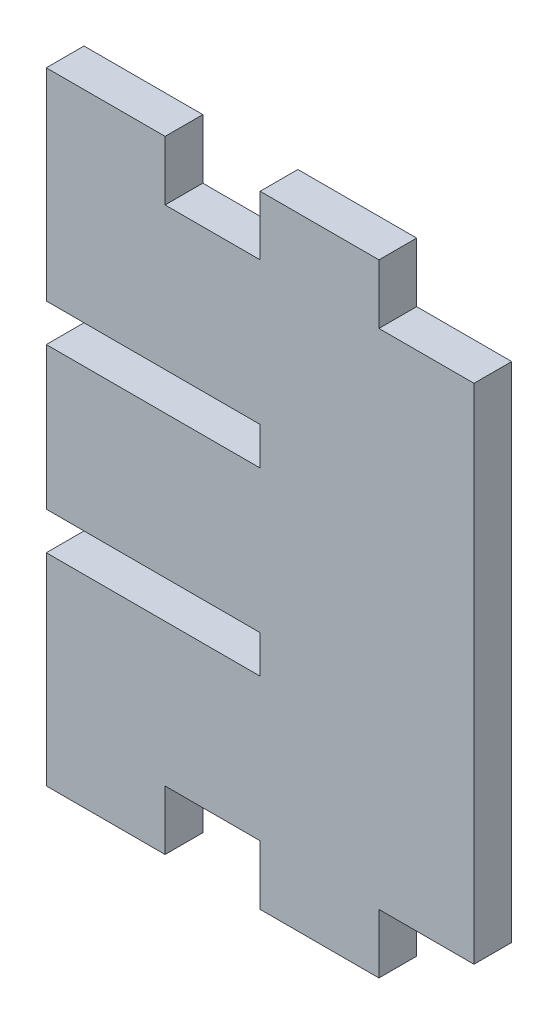
SolidWorks part; units mm, degrees
ref_plane "Front Plane" through (0, 0, 0) normal (0, 0, 1) x (1, 0, 0)
ref_plane "Top Plane" through (0, 0, 0) normal (0, 1, 0) x (1, 0, 0)
ref_plane "Right Plane" through (0, 0, 0) normal (1, 0, 0) x (0, 0, -1)
sketch "Sketch1" plane through (0, 0, 0) normal (0, 0, 1) x (1, 0, 0)
  line L0 (0, 0) -> (60.2571, 0) construction
  line L1 (55, 0) -> (-55, 0) construction
  line L2 (-18, -6) -> (-18, 6)
  line L3 (-18, 6) -> (0, 6)
  line L4 (0, 6) -> (0, 9.175)
  line L5 (0, 9.175) -> (-18, 9.175)
  line L6 (-18, 9.175) -> (-18, 26.175)
  line L7 (0, -55) -> (0, 55) construction
  line L8 (0, 1.5761) -> (0, 45.6913) construction
  line L9 (-18, 26.175) -> (-8, 26.175)
  line L10 (0, 26.175) -> (0, 21.175)
  line L11 (0, 21.175) -> (-8, 21.175)
  line L12 (-8, 21.175) -> (-8, 26.175)
  line L13 (0, 26.175) -> (10, 26.175)
  line L14 (10, 26.175) -> (10, 21.175)
  line L15 (10, 21.175) -> (18, 21.175)
  line L16 (18, 21.175) -> (18, -21.175)
  line L17 (-18, -6) -> (0, -6)
  line L18 (0, -6) -> (0, -9.175)
  line L19 (0, -9.175) -> (-18, -9.175)
  line L20 (-18, -9.175) -> (-18, -26.175)
  line L21 (0, -26.175) -> (0, -21.175)
  line L22 (-18, -26.175) -> (-8, -26.175)
  line L23 (10, -21.175) -> (18, -21.175)
  line L24 (10, -26.175) -> (10, -21.175)
  line L25 (0, -26.175) -> (10, -26.175)
  line L26 (-8, -21.175) -> (-8, -26.175)
  line L27 (0, -21.175) -> (-8, -21.175)
  line L28 (43.6365, 21.175) -> (43.537, 21.175)
  line L29 (0, -21.175) -> (0, -9.175) construction
  line L30 (0, -9.175) -> (-0.0397, -9.1768)
  point P23 (-18, 0)
  point P30 (18, 0)
  dimension "D1" = 36
  dimension "D2" = 3.175
  dimension "D3" = 5
  dimension "D4" = 12
  dimension "D5" = 10
  dimension "D6" = 12
  dimension "D7" = 8
extrude "Boss-Extrude2" add sketch "Sketch1" along normal blind 3.175 contours L27 L21 L25 L24 L23 L16 L15 L14 L13 L10 L11 L12 L9 L6 L5 L4 L3 L2 L17 L18 L19 L20 L22 L26 region at (0.142, 0, 0)
